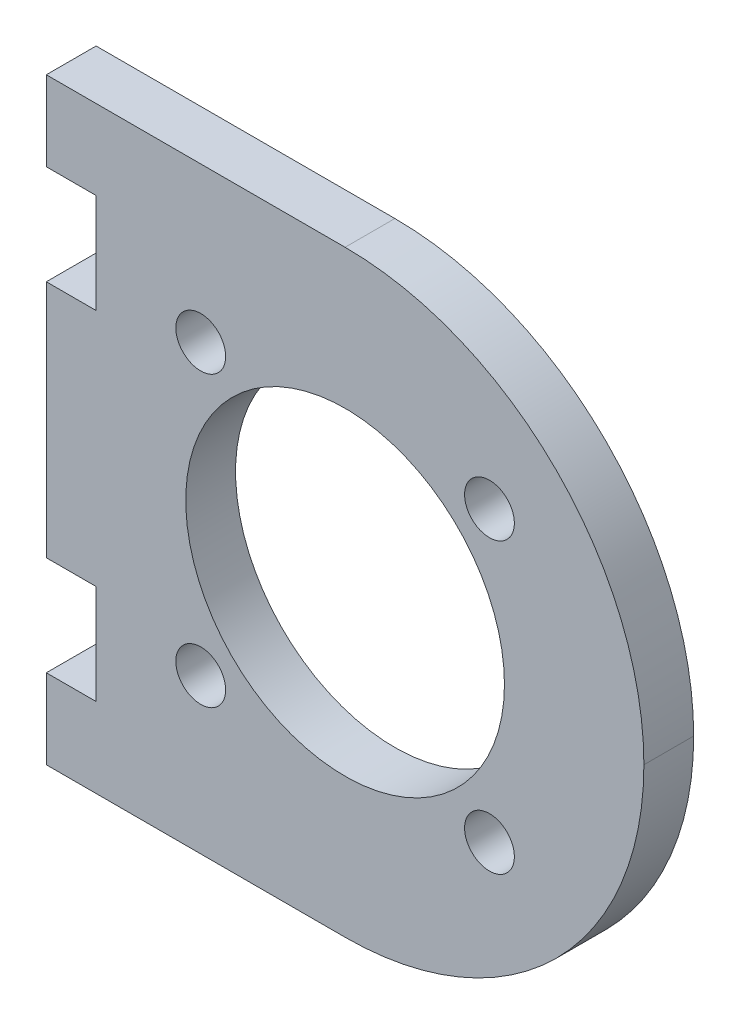
SolidWorks part; units mm, degrees
ref_plane "Front Plane" through (0, 0, 0) normal (1, 0, 0) x (0, 1, 0)
ref_plane "Top Plane" through (0, 0, 0) normal (0, 0, 1) x (0, 1, 0)
ref_plane "Right Plane" through (0, 0, 0) normal (0, 1, 0) x (-1, 0, 0)
sketch "Sketch1" plane through (0, 0, 0) normal (0, 0, 1) x (0, 1, 0)
  line L0 (0, 0) -> (0, 30) construction
  line L1 (-30, -30) -> (30, -30)
  line L2 (-30, -30) -> (-30, 30)
  line L3 (-30, 30) -> (-22, 30)
  line L4 (30, -30) -> (30, 30)
  line L5 (-30, -30) -> (30, 30) construction
  line L6 (-30, 30) -> (30, -30) construction
  line L7 (0, 30) -> (-12, 30) construction
  line L8 (-12, 30) -> (-12, 25)
  line L9 (-12, 25) -> (-22, 25)
  line L10 (-22, 25) -> (-22, 30)
  line L11 (-12, 30) -> (12, 30)
  line L12 (12, 30) -> (12, 25)
  line L13 (12, 25) -> (22, 25)
  line L14 (22, 25) -> (22, 30)
  line L15 (22, 30) -> (30, 30)
  circle A0 centre (0, 0) radius 16
  circle A1 centre (0, 0) radius 20.5 construction
  circle A2 centre (0, 20.5) radius 2.5 construction
  circle A3 centre (7.845, 18.9395) radius 2.5 construction
  circle A4 centre (14.4957, 14.4957) radius 2.5
  circle A5 centre (18.9395, 7.845) radius 2.5 construction
  circle A6 centre (20.5, 0) radius 2.5 construction
  circle A7 centre (18.9395, -7.845) radius 2.5 construction
  circle A8 centre (14.4957, -14.4957) radius 2.5
  circle A9 centre (7.845, -18.9395) radius 2.5 construction
  circle A10 centre (0, -20.5) radius 2.5 construction
  circle A11 centre (-7.845, -18.9395) radius 2.5 construction
  circle A12 centre (-14.4957, -14.4957) radius 2.5
  circle A13 centre (-18.9395, -7.845) radius 2.5 construction
  circle A14 centre (-20.5, 0) radius 2.5 construction
  circle A15 centre (-18.9395, 7.845) radius 2.5 construction
  circle A16 centre (-14.4957, 14.4957) radius 2.5
  circle A17 centre (-7.845, 18.9395) radius 2.5 construction
  point P0 (0, 0)
  point P43 (0, 0)
  dimension "D1" = 32
  dimension "D2" = 41
  dimension "D5" = 5
  dimension "D4" = 60
  dimension "D3" = 60
  dimension "D7" = 12
  dimension "D8" = 10
  dimension "D9" = 5
  dimension "D6" = 16
extrude "Boss-Extrude1" add sketch "Sketch1" along normal blind 5
fillet "Fillet1" radius 30 2 edges at (30, 30, 2.5) (30, -30, 2.5)
sketch "Sketch2" plane through (0, 0, 0) normal (0, 0, 1) x (0, 1, 0)
  line L1 (0, 0) -> (-4.5, 0) construction
  circle A0 centre (0, 0) radius 16 construction
  circle A1 centre (0, 0) radius 16
  circle A3 centre (-4.5, 0) radius 9.5 construction
  dimension "D3" = 4.5
  dimension "D1" = 19
